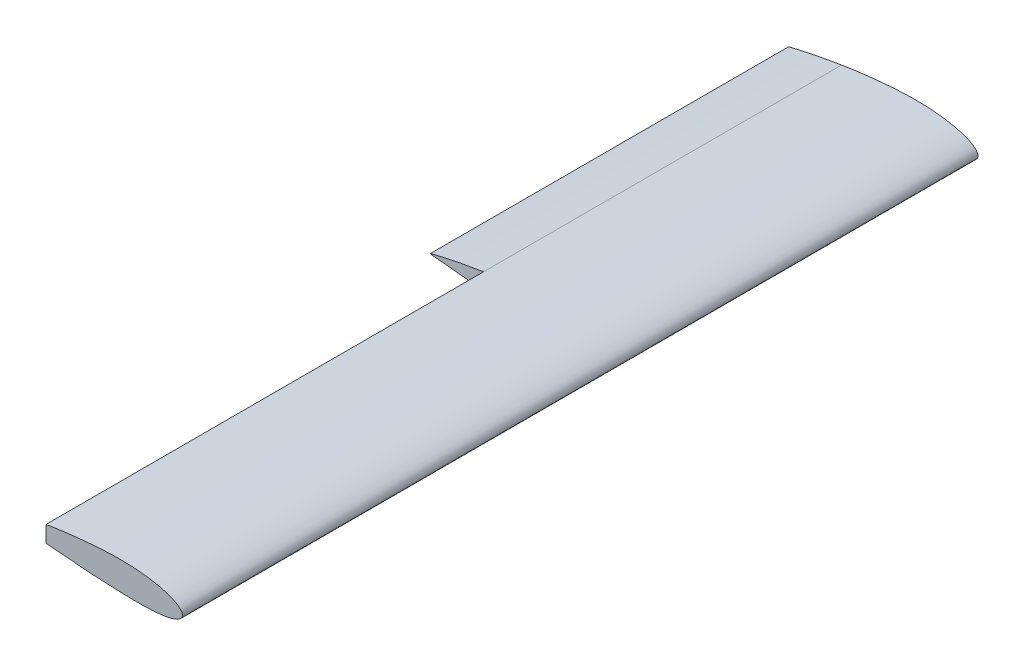
SolidWorks part; units mm, degrees
ref_plane "Front Plane" through (0, 0, 0) normal (0, 0, 1) x (1, 0, 0)
ref_plane "Top Plane" through (0, 0, 0) normal (0, 1, 0) x (1, 0, 0)
ref_plane "Right Plane" through (0, 0, 0) normal (1, 0, 0) x (0, 0, -1)
sketch "Sketch1" plane through (0, 0, 0) normal (0, 0, 1) x (1, 0, 0)
  line L0 (-191.9354, 15.416) -> (-191.9354, -7.6909)
  spline S0 degree 3 poles (-191.9354, 15.416) (-189.5243, 15.8004) (-183.84, 16.7066) (-174.7811, 18.0293) (-164.699, 19.4011) (-154.4132, 20.6737) (-143.9882, 21.8304) (-133.4887, 22.8492) (-122.9807, 23.7108) (-112.5154, 24.3961) (-102.1393, 24.8937) (-91.9165, 25.1258) (-81.9303, 25.09) (-72.2668, 24.7809) (-62.9911, 24.2008) (-54.1652, 23.3569) (-45.8482, 22.2615) (-38.0948, 20.9316) (-30.9554, 19.3888) (-24.475, 17.6581) (-18.6932, 15.7669) (-13.6432, 13.7442) (-9.3513, 11.6182) (-5.8361, 9.4143) (-3.1085, 7.1499) (-1.1753, 4.8279) (-0.0633, 2.4265) (0.145, -0.0146) (-0.5418, -2.3641) (-2.0929, -4.4987) (-4.4137, -6.4044) (-7.4763, -8.1169) (-11.2681, -9.647) (-15.7716, -10.9953) (-20.9621, -12.1581) (-26.8094, -13.1324) (-33.2789, -13.9168) (-40.3323, -14.5128) (-47.9288, -14.9252) (-56.0247, -15.1619) (-64.5743, -15.2345) (-73.5296, -15.1578) (-82.8407, -14.9489) (-92.4558, -14.628) (-102.3403, -14.213) (-112.4533, -13.7319) (-122.7326, -13.1417) (-133.0976, -12.467) (-143.4707, -11.7255) (-153.7893, -10.9348) (-163.9906, -10.111) (-174.0119, -9.2678) (-183.3072, -8.4625) (-189.2543, -7.9307) (-191.9354, -7.6909) knots 0 0 0 0 0.018424 0.043434 0.06908 0.095203 0.12164 0.148227 0.1748 0.201195 0.227364 0.253182 0.278347 0.30271 0.326128 0.348467 0.3696 0.389416 0.407811 0.424699 0.440008 0.453688 0.465715 0.476104 0.484928 0.49236 0.49873 0.504587 0.510443 0.516804 0.524199 0.532941 0.543186 0.554996 0.568376 0.583299 0.599709 0.617539 0.636704 0.657109 0.678651 0.701217 0.724685 0.748928 0.773811 0.799338 0.825326 0.851504 0.877716 0.9038 0.929596 0.954944 0.979688 1 1 1 1
extrude "Boss-Extrude1" add sketch "Sketch1" along normal blind 1120
sketch "Sketch2" plane through (0, 0, 0) normal (0, 0, 1) x (1, 0, 0)
  line L0 (-191.9354, 15.416) -> (-191.9354, -7.6909)
  line L1 (-266.577, 0.4257) -> (-266.577, -0.4189)
  spline S0 degree 3 poles (-191.9354, 15.416) (-192.6941, 15.2972) (-196.5004, 14.701) (-203.198, 13.5621) (-211.8684, 12.0329) (-220.0466, 10.5101) (-227.685, 9.0244) (-234.7376, 7.5953) (-241.1628, 6.245) (-246.9227, 4.9942) (-251.9835, 3.8631) (-256.316, 2.8703) (-259.895, 2.0327) (-262.7001, 1.365) (-264.7152, 0.8792) (-265.9195, 0.5864) (-266.4509, 0.4566) (-266.577, 0.4257) knots 0 0 0 0 0.030252 0.151774 0.267626 0.37709 0.479485 0.574175 0.66057 0.73813 0.806369 0.864859 0.913229 0.951173 0.978451 0.994887 1 1 1 1
  spline S1 degree 3 poles (-191.9354, -7.6909) (-192.4201, -7.6479) (-195.9505, -7.3341) (-202.3859, -6.745) (-211.0842, -5.9402) (-219.3093, -5.1646) (-227.0093, -4.427) (-234.1351, -3.7336) (-240.6411, -3.0907) (-246.4855, -2.5047) (-251.6304, -1.981) (-256.0423, -1.5274) (-259.6922, -1.1436) (-262.5569, -0.8499) (-264.6155, -0.6129) (-265.8584, -0.5128) (-266.419, -0.4184) (-266.5677, -0.4189) (-266.577, -0.4189) knots 0 0 0 0 0.019463 0.141781 0.258505 0.3689 0.472262 0.567931 0.655294 0.733785 0.802892 0.862162 0.911205 0.949694 0.977373 0.994054 0.999628 1 1 1 1
extrude "Boss-Extrude2" add sketch "Sketch2" along normal blind 504
sketch "Sketch3" plane through (0, 0, 0) normal (0, 0, 1) x (1, 0, 0)
  circle A0 centre (-79.973, 4.998) radius 12.7
extrude "Cut-Extrude1" cut sketch "Sketch3" along normal blind 801
ref_plane "Plane1" through (0, 0, 330.7) normal (0, 0, 1) x (1, 0, 0)
sketch "Sketch4" plane through (0, 0, 330.7) normal (0, 0, 1) x (1, 0, 0)
  line L0 (-95.973, -16.001) -> (-63.973, -16.001)
  line L1 (-63.973, -16.001) -> (-63.973, 20.698)
  line L2 (-63.973, 20.698) -> (-95.973, 20.698)
  line L3 (-95.973, 20.698) -> (-95.973, -16.001)
extrude "Cut-Extrude2" cut sketch "Sketch4" along normal blind 46
ref_plane "Plane2" through (0, 0, 330.7) normal (0, 0, 1) x (1, 0, 0)
sketch "Sketch5" plane through (0, 0, 330.7) normal (0, 0, 1) x (1, 0, 0)
  line L0 (-243.2616, -7.779) -> (-183.2616, -7.779)
  line L1 (-183.2616, -7.779) -> (-183.2616, 4.221)
  line L2 (-183.2616, 4.221) -> (-243.2616, 4.221)
  line L3 (-243.2616, 4.221) -> (-243.2616, -7.779)
extrude "Cut-Extrude3" cut sketch "Sketch5" along normal blind 46
ref_plane "Plane3" through (0, 0, 534.5) normal (0, 0, 1) x (1, 0, 0)
sketch "Sketch6" plane through (0, 0, 534.5) normal (0, 0, 1) x (1, 0, 0)
  line L0 (-173.617, -14.504) -> (-119.617, -14.504)
  line L1 (-119.617, -14.504) -> (-119.617, 14.596)
  line L2 (-119.617, 14.596) -> (-173.617, 14.596)
  line L3 (-173.617, 14.596) -> (-173.617, -14.504)
extrude "Cut-Extrude4" cut sketch "Sketch6" along normal blind 64
ref_plane "Plane4" through (0, 0, -0.5) normal (0, 0, 1) x (1, 0, 0)
sketch "Sketch7" plane through (0, 0, -0.5) normal (0, 0, 1) x (1, 0, 0)
  line L0 (-196.804, 0.599) -> (-176.404, 0.599)
  line L1 (-176.404, 0.599) -> (-176.404, 7.399)
  line L2 (-176.404, 7.399) -> (-196.804, 7.399)
  line L3 (-196.804, 7.399) -> (-196.804, 0.599)
extrude "Cut-Extrude5" cut sketch "Sketch7" along normal blind 26
